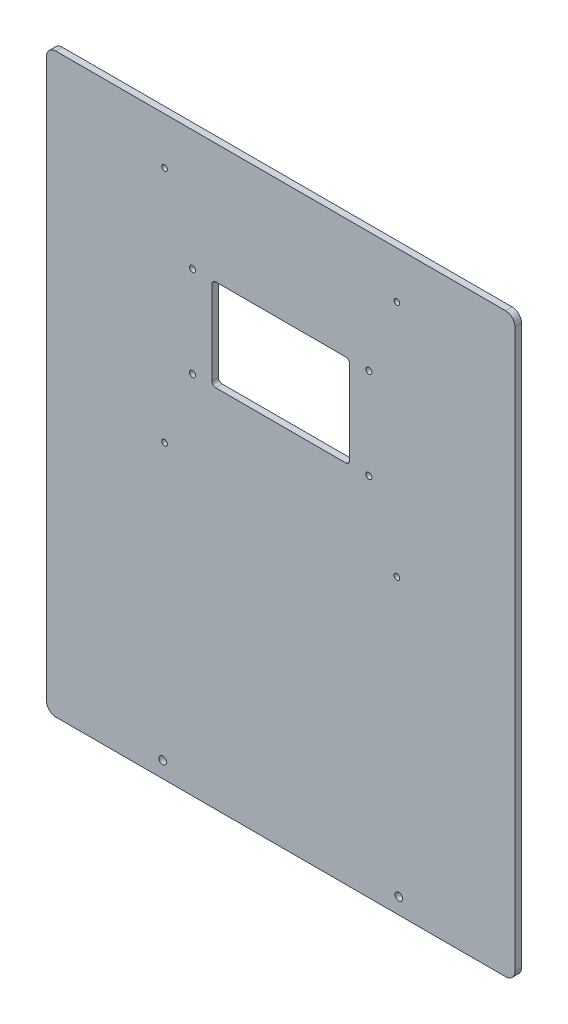
SolidWorks part; units mm, degrees
ref_plane "Plan de face" through (0, 0, 0) normal (0, 0, 1) x (1, 0, 0)
ref_plane "Plan de dessus" through (0, 0, 0) normal (0, 1, 0) x (1, 0, 0)
ref_plane "Plan de droite" through (0, 0, 0) normal (1, 0, 0) x (0, 0, -1)
sketch "Esquisse1" plane through (0, 0, 0) normal (0, 0, 1) x (1, 0, 0)
  line L1 (5, 0) -> (245, 0)
  line L2 (0, 5) -> (0, 302.81)
  line L3 (5, 307.81) -> (245, 307.81)
  line L4 (250, 5) -> (250, 302.81)
  arc A0 (250, 5) -> (245, 0) centre (245, 5) cw
  arc A1 (250, 302.81) -> (245, 307.81) centre (245, 302.81) ccw
  arc A2 (5, 0) -> (0, 5) centre (5, 5) cw
  arc A3 (5, 307.81) -> (0, 302.81) centre (5, 302.81) ccw
  point P9 (250, 307.81)
  point P12 (0, 0)
  point P15 (0, 307.81)
  dimension "D3" = 5
  dimension "D1" = 250
  dimension "D2" = 307.81
extrude "Boss.-Extru.1" add sketch "Esquisse1" along normal blind 3.5
sketch "Esquisse2" plane through (0, 0, 3.5) normal (0, 0, 1) x (1, 0, 0)
  line L0 (-35.7922, 8.5) -> (305.0105, 8.5) construction
  line L1 (5, 0) -> (245, 0) construction
  line L2 (0, 302.81) -> (0, 5) construction
  circle A0 centre (62, 8.5) radius 2
  circle A1 centre (188, 8.5) radius 2
  dimension "D2" = 4
  dimension "D5" = 4
  dimension "D1" = 8.5
  dimension "D3" = 62
  dimension "D4" = 126
extrude "Enlèv. mat.-Extru.1" cut sketch "Esquisse2" against normal through all
sketch "Esquisse3" plane through (0, 0, 3.5) normal (0, 0, 1) x (1, 0, 0)
  line L0 (125, 563.6946) -> (125, 51.9254) construction
  line L1 (245, 307.81) -> (5, 307.81) construction
  line L2 (21.2655, 219.31) -> (234.7147, 219.31) construction
  circle A0 centre (63, 155.81) radius 1.5
  circle A1 centre (63, 282.81) radius 1.5
  circle A2 centre (187, 282.81) radius 1.5
  circle A3 centre (187, 155.81) radius 1.5
  circle A4 centre (77.95, 243.58) radius 1.6
  circle A5 centre (172.05, 243.58) radius 1.6
  circle A6 centre (77.95, 195.04) radius 1.6
  circle A7 centre (172.05, 195.04) radius 1.6
  point P4 (125, 307.81)
  point P23 (0, 0)
  dimension "D3" = 3
  dimension "D4" = 3
  dimension "D5" = 3
  dimension "D6" = 3
  dimension "D17" = 3.2
  dimension "D18" = 3.2
  dimension "D19" = 3.2
  dimension "D20" = 3.2
  dimension "D15" = 24.27
  dimension "D1" = 124
  dimension "D2" = 124
  dimension "D7" = 127
  dimension "D8" = 127
  dimension "D9" = 25
  dimension "D10" = 62
  dimension "D11" = 94.1
  dimension "D12" = 47.05
  dimension "D13" = 48.54
  dimension "D14" = 48.54
  dimension "D16" = 47.05
  dimension "D21" = 24.27
  dimension "D22" = 63.5
  dimension "D23" = 25
extrude "Enlèv. mat.-Extru.2" cut sketch "Esquisse3" against normal through all
sketch "Esquisse4" plane through (0, 0, 3.5) normal (0, 0, 1) x (1, 0, 0)
  line L0 (125, 307.81) -> (125, 35.1539) construction
  line L1 (90.28, 243.79) -> (159.72, 243.79)
  line L2 (88.28, 241.79) -> (88.28, 196.83)
  line L3 (90.28, 194.83) -> (159.72, 194.83)
  line L4 (161.72, 241.79) -> (161.72, 196.83)
  line L5 (245, 307.81) -> (5, 307.81) construction
  line L6 (47.2411, 219.31) -> (206.1568, 219.31) construction
  circle A1 centre (77.95, 243.58) radius 1.6 construction
  arc A2 (159.72, 243.79) -> (161.72, 241.79) centre (159.72, 241.79) cw
  arc A3 (161.72, 196.83) -> (159.72, 194.83) centre (159.72, 196.83) cw
  arc A4 (90.28, 194.83) -> (88.28, 196.83) centre (90.28, 196.83) cw
  arc A5 (90.28, 243.79) -> (88.28, 241.79) centre (90.28, 241.79) ccw
  point P4 (125, 243.79)
  point P13 (88.28, 219.31)
  point P16 (161.72, 243.79)
  point P21 (88.28, 194.83)
  point P24 (88.28, 243.79)
  dimension "D3" = 24.27
  dimension "D4" = 2
  dimension "D1" = 73.44
  dimension "D2" = 48.96
extrude "Enlèv. mat.-Extru.3" cut sketch "Esquisse4" against normal through all
